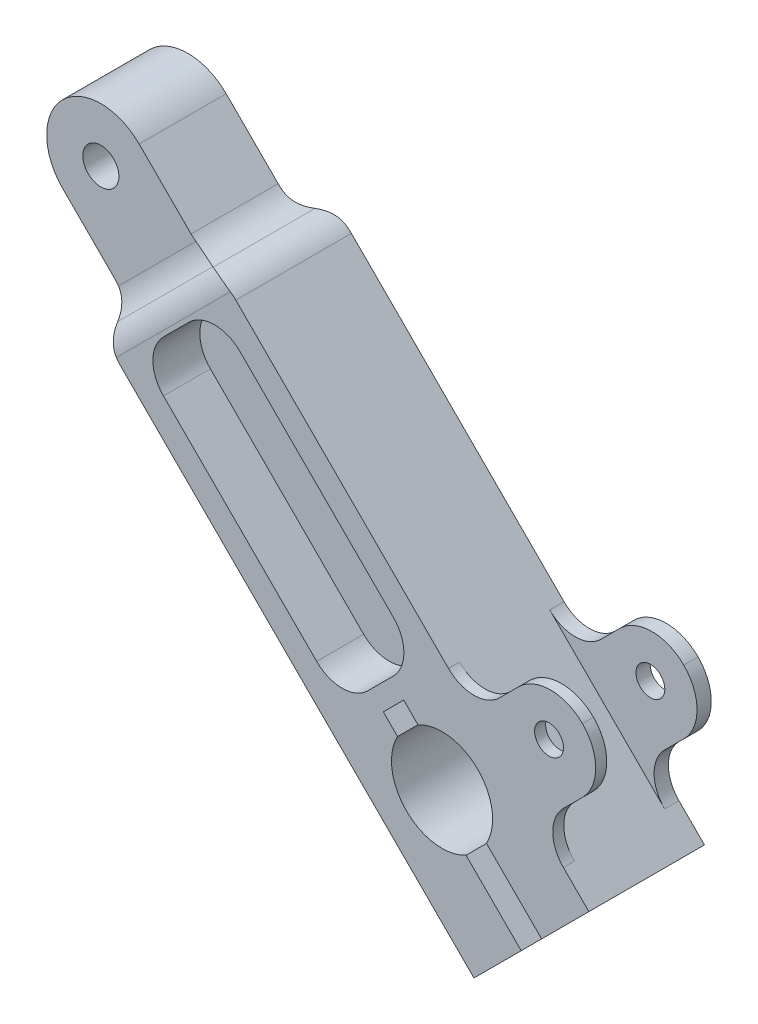
SolidWorks part; units mm, degrees
material "6061-T6 (SS)"
ref_plane "Front Plane" through (0, 0, 0) normal (0, 0, 1) x (1, 0, 0)
ref_plane "Top Plane" through (0, 0, 0) normal (0, 1, 0) x (1, 0, 0)
ref_plane "Right Plane" through (0, 0, 0) normal (1, 0, 0) x (0, 0, -1)
sketch "Sketch2" plane through (0, 0, 0) normal (0, 0, 1) x (1, 0, 0)
  line L0 (0, 0) -> (-234.0257, 0) construction
  line L1 (0, 0) -> (132.15, 132.15) construction
  line L2 (0, 0) -> (130.2279, -130.2279) construction
  line L3 (-10.6066, -10.6066) -> (10.6066, 10.6066) construction
  line L4 (-10.6066, -10.6066) -> (21.2132, -42.4264) construction
  line L5 (21.2132, -42.4264) -> (42.4264, -21.2132) construction
  line L6 (42.4264, -21.2132) -> (10.6066, 10.6066) construction
  line L7 (0, -21.2132) -> (21.2132, 0)
  line L9 (21.2132, 0) -> (53.033, -31.8198)
  line L10 (0, -21.2132) -> (31.8198, -53.033)
  line L11 (31.8198, -53.033) -> (26.5165, -58.3363)
  line L12 (114.318, -146.1378) -> (26.5165, -58.3363)
  line L13 (53.033, -31.8198) -> (58.3363, -26.5165)
  line L14 (128.4601, -96.6403) -> (58.3363, -26.5165)
  line L15 (146.1378, -114.318) -> (167.351, -93.1047)
  line L16 (167.351, -93.1047) -> (149.6733, -75.4271)
  line L17 (149.6733, -75.4271) -> (128.4601, -96.6403)
  line L18 (158.5121, -84.2659) -> (119.6213, -119.6213) construction
  line L19 (146.1378, -114.318) -> (160.2799, -128.4601)
  line L20 (114.318, -146.1378) -> (128.4601, -160.2799)
  line L21 (160.2799, -128.4601) -> (147.1984, -141.5416)
  line L22 (109.0147, -103.3578) -> (112.9628, -107.306)
  line L23 (103.3578, -109.0147) -> (109.0147, -103.3578)
  line L24 (103.3578, -109.0147) -> (107.306, -112.9628)
  line L25 (131.9365, -126.2797) -> (147.1984, -141.5416)
  line L26 (126.2797, -131.9365) -> (141.5416, -147.1984)
  line L27 (141.5416, -147.1984) -> (128.4601, -160.2799)
  line L28 (31.8198, -53.033) -> (53.033, -31.8198)
  line L29 (128.4601, -96.6403) -> (146.1378, -114.318)
  circle A0 centre (21.2132, -21.2132) radius 5
  circle A1 centre (149.2524, -92.6839) radius 4
  arc A2 (107.306, -112.9628) -> (126.2797, -131.9365) centre (119.6213, -119.6213) ccw
  arc A3 (131.9365, -126.2797) -> (112.9628, -107.306) centre (119.6213, -119.6213) ccw
  point P8 (0, 0)
  point P15 (10.6066, -10.6066)
  point P18 (130.2279, -130.2279)
  point P35 (111.5259, -126.9806)
  point P40 (106.1862, -106.1862)
  dimension "D4" = 10
  dimension "D5" = 15
  dimension "D12" = 8
  dimension "D13" = 12.5
  dimension "D14" = 28
  dimension "D1" = 184.17
  dimension "D2" = 30
  dimension "D3" = 45
  dimension "D6" = 15
  dimension "D7" = 30
  dimension "D8" = 45
  dimension "D9" = 45
  dimension "D10" = 30
  dimension "D11" = 25
  dimension "D15" = 20
  dimension "D17" = 19
extrude "Boss-Extrude1" add sketch "Sketch2" along normal blind 38 contours A3 L25 L21 L19 L29 L14 L13 L28 L11 L12 L20 L27 L26 A2 L24 L23 L22 region at (89.1363, -89.1363, 0)
extrude "Boss-Extrude2" add sketch "Sketch2<3>" along normal blind 6.5 contours L17 L29 L15 L16 A1 region at (139.4556, -86.4226, 0)
sketch "Sketch2<3>" plane through (0, 0, 0) normal (0, 0, 1) x (1, 0, 0) same geometry as "Sketch2"
fillet "Fillet1" radius 12.5 2 edges at (167.351, -93.1047, 3.25) (149.6733, -75.4271, 3.25)
ref_plane "Plane1" through (0, 0, 19) normal (0, 0, -1) x (-1, 0, 0)
mirror "Mirror1" about plane through (0, 0, 19) normal (0, 0, -1) of "Boss-Extrude2", "Fillet1"
sketch "Sketch3" plane through (42.4264, -42.4264, 0) normal (-0.7071, 0.7071, 0) x (0, 0, 1)
  line L0 (19, 73.5699) -> (19, -73.5699) construction
  line L1 (6.5, 15) -> (31.5, 15)
  line L2 (6.5, 15) -> (6.5, -15)
  line L3 (6.5, -15) -> (31.5, -15)
  line L4 (31.5, 15) -> (31.5, -15)
  line L5 (6.5, 15) -> (31.5, -15) construction
  line L6 (6.5, -15) -> (31.5, 15) construction
  point P0 (19, 0)
  dimension "D1" = 30
  dimension "D2" = 25
extrude "Boss-Extrude3" add sketch "Sketch3" along normal blind 45
sketch "Sketch4" plane through (0, 0, 31.5) normal (0, 0, 1) x (1, 0, 0)
  line L0 (10.6066, -10.6066) -> (31.8198, -31.8198) construction
  line L1 (0, -21.2132) -> (21.2132, 0) construction
  circle A0 centre (21.2132, -21.2132) radius 5
  dimension "D1" = 10
  dimension "D2" = 15
extrude "Cut-Extrude1" cut sketch "Sketch4" against normal through all
sketch "Sketch12" plane through (0, 0, 31.5) normal (0, 0, 1) x (1, 0, 0)
  line L4 (31.8198, -53.033) -> (53.033, -31.8198)
  line L5 (53.033, -31.8198) -> (21.2132, 0)
  line L6 (21.2132, 0) -> (0, -21.2132)
  line L7 (0, -21.2132) -> (31.8198, -53.033)
  line L8 (31.8198, -53.033) -> (53.033, -31.8198)
  line L9 (53.033, -31.8198) -> (21.2132, 0)
  line L10 (21.2132, 0) -> (0, -21.2132)
  line L11 (0, -21.2132) -> (31.8198, -53.033)
  dimension "D1" = 0
extrude "Cut-Extrude8" cut sketch "Sketch12" against normal up to surface (0.897 mm away)
fillet "Fillet2" radius 15 2 edges at (21.2132, 0, 18.5515) (0, -21.2132, 18.5515)
sketch "Sketch5" plane through (144.37, -144.37, 0) normal (0.7071, -0.7071, 0) x (0, 0, -1)
  line L0 (-38, -13.25) -> (0, -13.25) construction
  line L1 (-38, -4) -> (-38, -22.5) construction
  line L2 (0, -4) -> (0, -22.5) construction
  circle A0 centre (-27, -13.25) radius 4
  circle A1 centre (-13, -13.25) radius 4
  dimension "D1" = 8
  dimension "D2" = 8
  dimension "D3" = 14
  dimension "D4" = 11
fillet "Fillet3" radius 10 4 edges at (128.4601, -96.6403, 34.75) (128.4601, -96.6403, 3.25) (146.1378, -114.318, 34.75) (146.1378, -114.318, 3.25)
sketch "Sketch8" plane through (-15.9099, -15.9099, 0) normal (-0.7071, -0.7071, 0) x (0, 0, 1)
  circle A0 centre (22.0722, -191.8383) radius 4.1672 construction
  circle A1 centre (22.0722, -151.8383) radius 4.1672 construction
  circle A2 centre (22.0722, -191.8383) radius 4.1672
  circle A3 centre (22.0722, -151.8383) radius 4.1672
extrude "Cut-Extrude4" cut sketch "Sketch8" against normal blind 10
sketch "Sketch9" plane through (0, 0, 0) normal (0, 0, -1) x (-1, 0, 0)
  line L0 (-128.4601, -160.2799) -> (-26.5165, -58.3363)
  line L1 (-128.4601, -160.2799) -> (-184.1342, -104.6058)
  line L2 (-26.5165, -58.3363) -> (-82.1906, -2.6622)
  line L3 (-184.1342, -104.6058) -> (-82.1906, -2.6622)
extrude "Cut-Extrude5" cut sketch "Sketch9" against normal up to surface (2.5515 mm away) contours L0 L1 L3 L2
sketch "Sketch10" plane through (0, 0, 38) normal (0, 0, 1) x (1, 0, 0)
  line L0 (128.4601, -160.2799) -> (26.5165, -58.3363)
  line L1 (128.4601, -160.2799) -> (184.01, -104.73)
  line L2 (26.5165, -58.3363) -> (82.0664, -2.7864)
  line L3 (184.01, -104.73) -> (82.0664, -2.7864)
extrude "Cut-Extrude6" cut sketch "Sketch10" against normal up to surface (3.4485 mm away)
sketch "Sketch11" plane through (0, 0, 2.5515) normal (0, 0, -1) x (-1, 0, 0)
  line L0 (-106.1862, -106.1862) -> (-42.4264, -42.4264)
  line L1 (-103.3578, -109.0147) -> (-109.0147, -103.3578) construction
  line L2 (-26.5165, -58.3363) -> (-58.3363, -26.5165) construction
  line L3 (-88.4485, -109.6617) -> (-109.6617, -88.4485)
  line L4 (-88.4485, -109.6617) -> (-38.951, -60.1642)
  line L5 (-109.6617, -88.4485) -> (-60.1642, -38.951)
  line L6 (-38.951, -60.1642) -> (-60.1642, -38.951)
  line L7 (-88.4485, -109.6617) -> (-60.1642, -38.951) construction
  line L8 (-109.6617, -88.4485) -> (-38.951, -60.1642) construction
  line L9 (-88.4485, -109.6617) -> (-109.6617, -88.4485)
  line L10 (-88.4485, -109.6617) -> (-91.984, -113.1972)
  line L11 (-109.6617, -88.4485) -> (-113.1972, -91.984)
  line L12 (-91.984, -113.1972) -> (-113.1972, -91.984)
  line L13 (-74.3063, -74.3063) -> (-63.6997, -84.9129)
  line L14 (-38.951, -60.1642) -> (-60.1642, -38.951)
  line L15 (-38.951, -60.1642) -> (-35.4154, -56.6286)
  line L16 (-60.1642, -38.951) -> (-56.6286, -35.4154)
  line L17 (-35.4154, -56.6286) -> (-56.6286, -35.4154)
  point P7 (-74.3063, -74.3063)
  dimension "D1" = 70
  dimension "D2" = 30
  dimension "D3" = 5
  dimension "D4" = 90
  dimension "D5" = 5
extrude "Cut-Extrude7" cut sketch "Sketch11" against normal blind 13 contours L4 L6 L0 L3 | L0 L6 L5 L3 | L12 L0 L3 L11 | L12 L10 L3 L0 | L13 L0 L3 L4 | L14 L15 L17 L16 region at (106.1261, -95.5195, 2.5515) region at (95.5195, -106.1261, 2.5515) region at (79.6096, -69.003, 2.5515) region at (81.3774, -91.984, 2.5515) region at (56.6286, -67.2352, 2.5515)
fillet "Fillet4" radius 10 4 edges at (91.984, -113.1972, 9.0515) (113.1972, -91.984, 9.0515) (35.4154, -56.6286, 9.0515) (56.6286, -35.4154, 9.0515)
fillet "Fillet6" radius 10 4 edges at (31.8198, -53.033, 18.5515) (53.033, -31.8198, 18.5515) (42.4264, -42.4264, 6.5) (42.4264, -42.4264, 30.603)
fillet "Fillet7" radius 10 4 edges at (58.3363, -26.5165, 18.5515) (26.5165, -58.3363, 18.5515) (42.4264, -42.4264, 2.5515) (42.4264, -42.4264, 34.5515)
ref_plane "Plane2" through (0, 0, 18.5515) normal (0, 0, -1) x (-1, 0, 0)
mirror "Mirror2" about plane through (0, 0, 18.5515) normal (0, 0, -1) of "Fillet4", "Cut-Extrude7"
